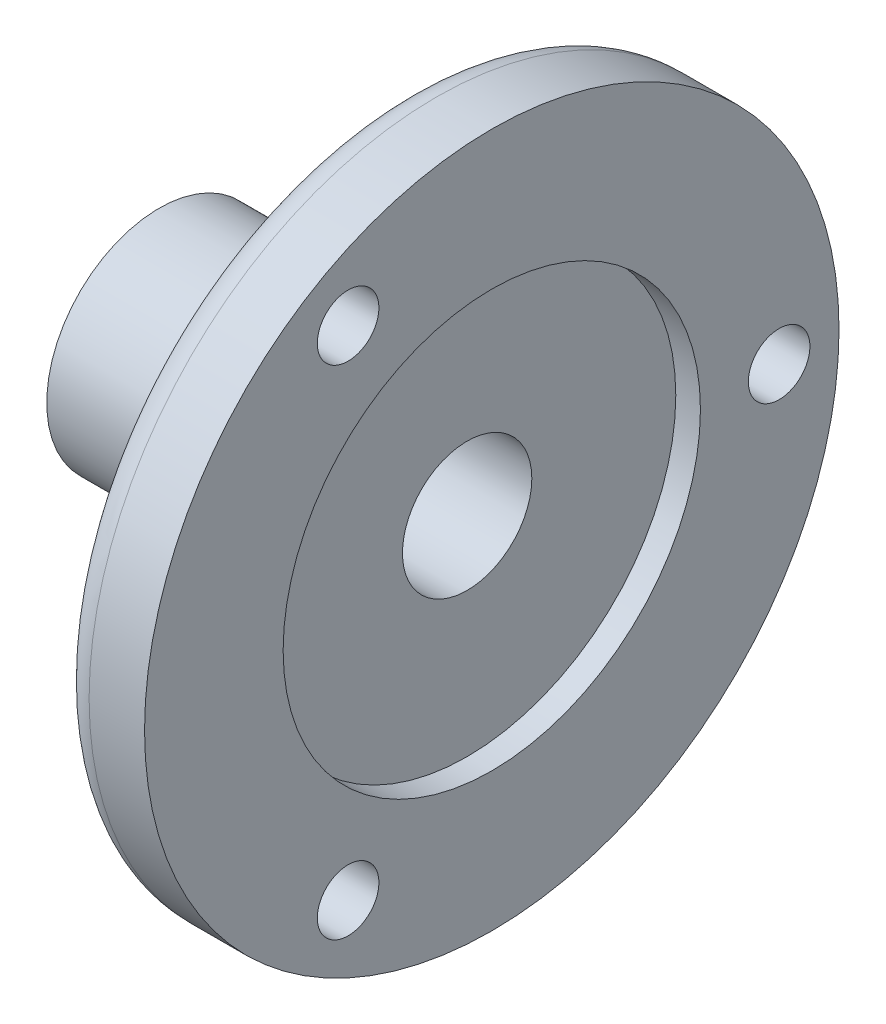
SolidWorks part; units mm, degrees
ref_plane "Front Plane" through (0, 0, 0) normal (0, 0, 1) x (1, 0, 0)
ref_plane "Top Plane" through (0, 0, 0) normal (0, 1, 0) x (1, 0, 0)
ref_plane "Right Plane" through (0, 0, 0) normal (1, 0, 0) x (0, 0, -1)
sketch "Sketch3" plane through (0, 0, 0) normal (1, 0, 0) x (0, 0, -1)
  circle A0 centre (0, 0) radius 3.65
  circle A1 centre (0, 0) radius 2.1
  dimension "D1" = 7.3
  dimension "D2" = 4.2
extrude "Boss-Extrude3" add sketch "Sketch3" along normal blind 10 contours A1 | A0 region at (0, 0, 0)
sketch "Sketch10" plane through (10, 0, 0) normal (1, 0, 0) x (0, 0, -1)
  circle A0 centre (0, 0) radius 11.275
  circle A1 centre (0, 0) radius 2.1
  circle A2 centre (0, 0) radius 3.65
  circle M5 centre (0, 0) radius 2.1
  dimension "D1" = 1.55
extrude "Boss-Extrude5" add sketch "Sketch10" against normal blind 2 contours M5 | A0 region at (10, 0, 0)
sketch "Sketch11" plane through (10, 0, 0) normal (1, 0, 0) x (0, 0, -1)
  circle A0 centre (0, 0) radius 6.775
  circle A1 centre (0, 0) radius 11.275
  circle M2 centre (0, 0) radius 2.1
extrude "Boss-Extrude6" add sketch "Sketch11" along normal blind 0.8 contours M2 | A0 M2 | A1 region at (10, 0, 6.5834) region at (10, 0, 0)
sketch "Sketch12" plane through (10.8, 0, 0) normal (1, 0, 0) x (0, 0, -1)
  line L1 (9.33, 0) -> (-4.665, 8.08)
  line L2 (-4.665, 8.08) -> (-4.665, -8.08)
  line L3 (-4.665, -8.08) -> (9.33, 0)
  circle A0 centre (0, 0) radius 4.665 construction
  circle A1 centre (0, 0) radius 11.275 construction
  circle A2 centre (-4.665, 8.08) radius 1
  circle A3 centre (-4.665, -8.08) radius 1
  circle A4 centre (9.33, 0) radius 1
  dimension "D1" = 9.33
extrude "Cut-Extrude2" cut sketch "Sketch12" against normal blind 2.75 contours L2 A3 L3 | L3 A4 L1 | L1 A4 L3 | L3 A3 L2 | A2 region at (10.8, 0, -8.6934) region at (10.8, 0, -9.4573) region at (10.8, -8.1903, 4.7287) region at (10.8, -7.5287, 4.3467)
fillet "Fillet3" radius 1 1 edges at (8, 0, -11.275)
